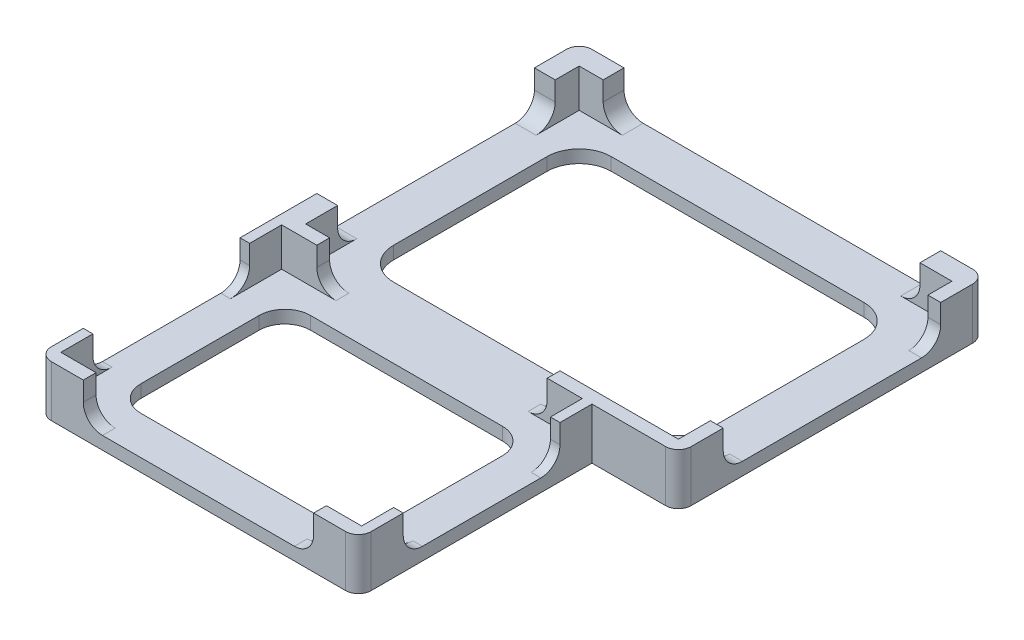
SolidWorks part; units mm, degrees
ref_plane "Front Plane" through (0, 0, 0) normal (0, 0, 1) x (1, 0, 0)
ref_plane "Top Plane" through (0, 0, 0) normal (0, 1, 0) x (1, 0, 0)
ref_plane "Right Plane" through (0, 0, 0) normal (1, 0, 0) x (0, 0, -1)
sketch "Sketch1" plane through (0, 0, 0) normal (0, 1, 0) x (1, 0, 0)
  line L1 (0, 0) -> (63.5, 0)
  line L2 (0, 0) -> (0, 48)
  line L3 (0, 48) -> (63.5, 48)
  line L4 (63.5, 0) -> (63.5, 48)
  dimension "D1" = 63.5
  dimension "D2" = 48
extrude "Boss-Extrude6" add sketch "Sketch1" along normal blind 21
sketch "Sketch5" plane through (0, 0, 0) normal (0, -1, 0) x (-1, 0, 0)
  line L1 (0, 0) -> (-50, 0)
  line L2 (0, 0) -> (0, -38.5)
  line L3 (0, -38.5) -> (-50, -38.5)
  line L4 (-50, 0) -> (-50, -38.5)
  dimension "D1" = 50
  dimension "D2" = 38.5
extrude "Boss-Extrude7" add sketch "Sketch5" against normal blind 11.5
sketch "Sketch6" plane through (0, 21, 0) normal (0, 1, 0) x (1, 0, 0)
  line L0 (63.5, 0) -> (63.5, 48) construction
  line L1 (61.5, 2) -> (2, 2)
  line L2 (61.5, 2) -> (61.5, 46)
  line L3 (61.5, 46) -> (2, 46)
  line L4 (2, 2) -> (2, 46)
  line L5 (63.5, 48) -> (0, 48) construction
  line L6 (0, 0) -> (63.5, 0) construction
  line L7 (0, 48) -> (0, 0) construction
  dimension "D1" = 2
  dimension "D2" = 2
  dimension "D3" = 2
  dimension "D4" = 2
extrude "Cut-Extrude1" cut sketch "Sketch6" against normal blind 19
sketch "Sketch7" plane through (0, 11.5, 0) normal (0, 1, 0) x (1, 0, 0)
  line L0 (50, 0) -> (50, -38.5) construction
  line L1 (48, -34.5) -> (2, -34.5)
  line L2 (48, -34.5) -> (48, 0)
  line L3 (48, 0) -> (2, 0)
  line L4 (2, -34.5) -> (2, 0)
  line L5 (0, -38.5) -> (0, 0) construction
  line L6 (50, -38.5) -> (0, -38.5) construction
  line L7 (0, 0) -> (50, 0) construction
  dimension "D1" = 2
  dimension "D2" = 2
  dimension "D3" = 4
  dimension "D4" = 0
extrude "Cut-Extrude2" cut sketch "Sketch7" against normal blind 9.5
sketch "Sketch8" plane through (0, 0, 38.5) normal (0, 0, 1) x (1, 0, 0)
  line L1 (50, 11.5) -> (0, 11.5)
  line L2 (50, 11.5) -> (50, 0)
  line L3 (50, 0) -> (0, 0)
  line L4 (0, 11.5) -> (0, 0)
extrude "Cut-Extrude4" cut sketch "Sketch8" against normal blind 2 contours L2 L1 L4 L3
sketch "Sketch10" plane through (0, 2, 0) normal (0, 1, 0) x (1, 0, 0)
  line L0 (2, 2) -> (61.5, 2) construction
  line L1 (12, 7) -> (51.5, 7)
  line L2 (7, 12) -> (7, 36)
  line L3 (12, 41) -> (51.5, 41)
  line L4 (56.5, 12) -> (56.5, 36)
  line L5 (2, 46) -> (2, 2) construction
  line L6 (61.5, 2) -> (61.5, 46) construction
  line L7 (61.5, 46) -> (2, 46) construction
  arc A0 (12, 7) -> (7, 12) centre (12, 12) cw
  arc A1 (7, 36) -> (12, 41) centre (12, 36) cw
  arc A2 (51.5, 41) -> (56.5, 36) centre (51.5, 36) cw
  arc A3 (51.5, 7) -> (56.5, 12) centre (51.5, 12) ccw
  dimension "D5" = 5
  dimension "D6" = 5
  dimension "D7" = 5
  dimension "D8" = 5
  dimension "D1" = 5
  dimension "D2" = 5
  dimension "D3" = 5
  dimension "D4" = 5
extrude "Cut-Extrude6" cut sketch "Sketch10" against normal blind 2
sketch "Sketch11" plane through (0, 2, 0) normal (0, 1, 0) x (1, 0, 0)
  line L0 (2, 0) -> (2, -34.5) construction
  line L1 (10, -30.5) -> (40, -30.5)
  line L2 (6, -26.5) -> (6, -8)
  line L3 (10, -4) -> (40, -4)
  line L4 (44, -26.5) -> (44, -8)
  line L5 (2, -34.5) -> (48, -34.5) construction
  line L6 (48, 0) -> (2, 0) construction
  line L7 (48, -34.5) -> (48, 0) construction
  arc A0 (10, -30.5) -> (6, -26.5) centre (10, -26.5) cw
  arc A1 (6, -8) -> (10, -4) centre (10, -8) cw
  arc A2 (40, -4) -> (44, -8) centre (40, -8) cw
  arc A3 (40, -30.5) -> (44, -26.5) centre (40, -26.5) ccw
  dimension "D5" = 4
  dimension "D6" = 4
  dimension "D7" = 4
  dimension "D8" = 4
  dimension "D1" = 4
  dimension "D2" = 4
  dimension "D3" = 4
  dimension "D4" = 4
extrude "Cut-Extrude7" cut sketch "Sketch11" against normal blind 2
sketch "Sketch13" plane through (63.5, 0, 0) normal (1, 0, 0) x (0, 0, -1)
  line L0 (0, 21) -> (48, 21) construction
  line L1 (7, 21) -> (41, 21)
  line L2 (7, 21) -> (7, 5)
  line L3 (10, 2) -> (38, 2)
  line L4 (41, 21) -> (41, 5)
  line L5 (2, 2) -> (2, 21) construction
  line L6 (46, 2) -> (46, 21) construction
  line L7 (2, 2) -> (46, 2) construction
  arc A0 (7, 5) -> (10, 2) centre (10, 5) ccw
  arc A1 (38, 2) -> (41, 5) centre (38, 5) ccw
  dimension "D5" = 3
  dimension "D6" = 3
  dimension "D1" = 0
  dimension "D2" = 5
  dimension "D3" = 5
  dimension "D4" = 0
extrude "Cut-Extrude10" cut sketch "Sketch13" against normal blind 72 contours A1 L3 A0 L2 L1 L4
sketch "Sketch14" plane through (0, 0, -48) normal (0, 0, -1) x (-1, 0, 0)
  line L0 (-61.5, 2) -> (-61.5, 21) construction
  line L1 (-56.5, 21) -> (-7, 21)
  line L2 (-56.5, 21) -> (-56.5, 5)
  line L3 (-53.5, 2) -> (-10, 2)
  line L4 (-7, 21) -> (-7, 5)
  line L5 (-2, 2) -> (-2, 21) construction
  line L6 (-61.5, 2) -> (-2, 2) construction
  line L7 (-63.5, 21) -> (0, 21) construction
  arc A0 (-56.5, 5) -> (-53.5, 2) centre (-53.5, 5) ccw
  arc A1 (-10, 2) -> (-7, 5) centre (-10, 5) ccw
  dimension "D5" = 3
  dimension "D6" = 3
  dimension "D1" = 5
  dimension "D2" = 5
  dimension "D3" = 0
  dimension "D4" = 0
extrude "Cut-Extrude11" cut sketch "Sketch14" against normal blind 38
sketch "Sketch16" plane through (63.5, 0, 0) normal (1, 0, 0) x (0, 0, -1)
  line L0 (41, 21) -> (41, 5) construction
  line L1 (-19, 14.5) -> (48, 14.5)
  line L2 (-19, 14.5) -> (-19, 21)
  line L3 (-19, 21) -> (48, 21)
  line L4 (48, 14.5) -> (48, 21)
  line L5 (48, 21) -> (48, 0) construction
  line L6 (41, 21) -> (48, 21) construction
  line L7 (38, 2) -> (46, 2) construction
  dimension "D1" = 60
  dimension "D2" = 0
  dimension "D3" = 0
  dimension "D4" = 12.5
extrude "Cut-Extrude13" cut sketch "Sketch16" against normal blind 79
sketch "Sketch17" plane through (0, 0, -2) normal (0, 0, -1) x (-1, 0, 0)
  line L0 (-2, 14.5) -> (-61.5, 14.5) construction
  line L1 (-43, 14.5) -> (-7, 14.5)
  line L2 (-43, 14.5) -> (-43, 5)
  line L3 (-40, 2) -> (-10, 2)
  line L4 (-7, 14.5) -> (-7, 5)
  line L5 (-2, 2) -> (-2, 14.5) construction
  line L6 (-48, 2) -> (-48, 11.5) construction
  line L7 (-48, 2) -> (-2, 2) construction
  arc A0 (-10, 2) -> (-7, 5) centre (-10, 5) ccw
  arc A1 (-43, 5) -> (-40, 2) centre (-40, 5) ccw
  dimension "D5" = 3
  dimension "D6" = 3
  dimension "D1" = 0
  dimension "D2" = 5
  dimension "D3" = 5
  dimension "D4" = 0
extrude "Cut-Extrude14" cut sketch "Sketch17" against normal blind 79
sketch "Sketch18" plane through (50, 0, 0) normal (1, 0, 0) x (0, 0, -1)
  line L0 (0, 11.5) -> (-36.5, 11.5) construction
  line L1 (-29.5, 11.5) -> (-5, 11.5)
  line L2 (-29.5, 11.5) -> (-29.5, 5)
  line L3 (-26.5, 2) -> (-8, 2)
  line L4 (-5, 11.5) -> (-5, 5)
  line L5 (0, 0) -> (-36.5, 0) construction
  line L6 (-34.5, 2) -> (-34.5, 11.5) construction
  line L7 (0, 2) -> (0, 11.5) construction
  arc A0 (-29.5, 5) -> (-26.5, 2) centre (-26.5, 5) ccw
  arc A1 (-8, 2) -> (-5, 5) centre (-8, 5) ccw
  dimension "D5" = 3
  dimension "D6" = 3
  dimension "D1" = 0
  dimension "D2" = 2
  dimension "D3" = 5
  dimension "D4" = 5
extrude "Cut-Extrude15" cut sketch "Sketch18" against normal blind 79
fillet "Fillet1" radius 2 1 edges at (50, 5.75, 36.5) type face fillet first side face at (50, 5.8757, 17.65) second side face at (25, 5.8757, 36.5)
fillet "Fillet2" radius 2 1 edges at (0, 5.75, 36.5) type face fillet first side face at (24.6, 5.8757, 36.5) second side face at (0, 7.1953, -3.5278)
fillet "Fillet3" radius 2 1 edges at (0, 7.25, -48) type face fillet first side face at (0, 7.1953, -3.75) second side face at (31.75, 7.0757, -48)
fillet "Fillet4" radius 2 1 edges at (63.5, 7.25, -48) type face fillet first side face at (32.15, 7.0757, -48) second side face at (63.5, 7.0757, -24)
fillet "Fillet5" radius 2 1 edges at (63.5, 7.25, 0) type face fillet first side face at (63.5, 7.0757, -23.6) second side face at (49.9579, 6.7087, 0)
sketch "Sketch19" plane through (50, 0, 0) normal (1, 0, 0) x (0, 0, -1)
  line L0 (-29.5, 11.5) -> (-34.5, 11.5) construction
  line L1 (-36.5, 9.5) -> (0, 9.5)
  line L2 (-36.5, 9.5) -> (-36.5, 11.5)
  line L3 (-36.5, 11.5) -> (0, 11.5)
  line L4 (0, 9.5) -> (0, 11.5)
  line L5 (-26.5, 2) -> (-8, 2) construction
  line L6 (-36.5, 5) -> (-36.5, 11.5) construction
  line L7 (0, 11.5) -> (0, 0) construction
  dimension "D1" = 0
  dimension "D2" = 7.5
  dimension "D3" = 0
  dimension "D4" = 0
extrude "Cut-Extrude17" cut sketch "Sketch19" against normal blind 79
fillet "Fillet6" radius 5 1 edges at (1, 9.5, 0) type face fillet first side face at (1, 9.5, 2.5) second side face at (3.9112, 8.0541, 0)
fillet "Fillet7" radius 5 1 edges at (49, 9.5, 0) type face fillet first side face at (49, 9.5, 2.5) second side face at (49.5135, 6.2643, 0)
sketch "Sketch20" plane through (0, 2, 0) normal (0, 1, 0) x (1, 0, 0)
  line L0 (10, 0) -> (2, 0) construction
  line L1 (23, 0) -> (27, 0)
  line L2 (23, 0) -> (23, 2)
  line L3 (23, 2) -> (27, 2)
  line L4 (27, 0) -> (27, 2)
  line L5 (10, 0) -> (10, 2) construction
  line L6 (40, 0) -> (40, 2) construction
  dimension "D1" = 2
  dimension "D2" = 0
  dimension "D3" = 13
  dimension "D4" = 13
extrude "Boss-Extrude16" add sketch "Sketch20" along normal blind 18
sketch "Sketch30" plane through (0, 0, 0) normal (0, 0, 1) x (1, 0, 0)
  line L0 (23, 20) -> (23, 2) construction
  line L1 (27, 20) -> (23, 20)
  line L2 (27, 20) -> (27, 19)
  line L3 (27, 19) -> (23, 19)
  line L4 (23, 20) -> (23, 19)
  dimension "D1" = 1
extrude "Boss-Extrude17" add sketch "Sketch30" along normal blind 2
sketch "Sketch33" plane through (0, 0, 0) normal (0, 0, 1) x (1, 0, 0)
  line L0 (23, 19) -> (23, 2) construction
  line L1 (23, 12) -> (27, 12)
  line L2 (23, 12) -> (23, 13.5)
  line L3 (23, 13.5) -> (27, 13.5)
  line L4 (27, 12) -> (27, 13.5)
  line L5 (27, 19) -> (27, 2) construction
  line L6 (23, 2) -> (27, 2) construction
  dimension "D1" = 10
  dimension "D2" = 1.5
extrude "Boss-Extrude18" add sketch "Sketch33" along normal blind 4
sketch "Sketch34" plane through (0, 0, -2) normal (0, 0, -1) x (-1, 0, 0)
  line L0 (-23, 20) -> (-23, 2) construction
  line L1 (-27, 20) -> (-23, 20)
  line L2 (-27, 20) -> (-27, 19)
  line L3 (-27, 19) -> (-23, 19)
  line L4 (-23, 20) -> (-23, 19)
  dimension "D1" = 1
extrude "Boss-Extrude19" add sketch "Sketch34" along normal blind 2
sketch "Sketch36" plane through (0, 0, 2) normal (0, 0, 1) x (1, 0, 0)
  line L1 (27, 19) -> (23, 19)
  line L2 (27, 19) -> (27, 20)
  line L3 (27, 20) -> (23, 20)
  line L4 (23, 19) -> (23, 20)
extrude "Cut-Extrude21" cut sketch "Sketch36" against normal blind 2
sketch "Sketch37" plane through (27, 0, 0) normal (1, 0, 0) x (0, 0, -1)
  line L0 (0, 20) -> (4, 19.2571)
  line L1 (0, 20) -> (4, 20) construction
  line L2 (4, 20) -> (4, 19) construction
  line L3 (4, 19.2571) -> (4, 20)
  line L4 (4, 20) -> (0, 20)
extrude "Cut-Extrude22" cut sketch "Sketch37" against normal blind 7
sketch "Sketch38" plane through (27, 0, 0) normal (1, 0, 0) x (0, 0, -1)
  line L0 (0, 13.5) -> (-4, 10.2256)
  line L1 (-4, 12) -> (-4, 13.5) construction
  line L2 (-4, 10.2256) -> (-4, 13.5)
  line L3 (-4, 13.5) -> (0, 13.5)
extrude "Cut-Extrude25" cut sketch "Sketch38" against normal blind 7
sketch "Sketch39" plane through (27, 0, 0) normal (1, 0, 0) x (0, 0, -1)
  line L0 (0, 2) -> (2, 2) construction
  line L1 (-1.8324, 20) -> (7.3799, 20)
  line L2 (-1.8324, 20) -> (-1.8324, 2)
  line L3 (-1.8324, 2) -> (7.3799, 2)
  line L4 (7.3799, 20) -> (7.3799, 2)
  dimension "D1" = 0
  dimension "D2" = 0
  dimension "D3" = 0
extrude "Cut-Extrude26" cut sketch "Sketch39" against normal blind 10
sketch "Sketch40" plane through (0, 0, -48) normal (0, 0, -1) x (-1, 0, 0)
  line L0 (-56.5, 14.5) -> (-61.5, 14.5) construction
  line L1 (-63.5, 14.5) -> (0, 14.5)
  line L2 (-63.5, 14.5) -> (-63.5, 8)
  line L3 (-63.5, 8) -> (0, 8)
  line L4 (0, 14.5) -> (0, 8)
  line L5 (-63.5, 14.5) -> (-63.5, 0) construction
  line L6 (0, 14.5) -> (0, 0) construction
  line L7 (-53.5, 2) -> (-10, 2) construction
  point P9 (0, 11.25)
  dimension "D1" = 0
  dimension "D2" = 0
  dimension "D3" = 0
  dimension "D4" = 6
extrude "Cut-Extrude27" cut sketch "Sketch40" against normal blind 117
sketch "Sketch44" plane through (2, 0, 0) normal (1, 0, 0) x (0, 0, -1)
  line L1 (-34.5, 8) -> (0, 8)
  line L2 (-34.5, 8) -> (-34.5, 2)
  line L3 (-34.5, 2) -> (0, 2)
  line L4 (0, 8) -> (0, 2)
extrude "Cut-Extrude30" cut sketch "Sketch44" against normal blind 0.5
sketch "Sketch45" plane through (48, 0, 0) normal (-1, 0, 0) x (0, 0, 1)
  line L0 (8, 2) -> (0, 2) construction
  line L1 (34.5, 8) -> (0, 8)
  line L2 (34.5, 8) -> (34.5, 2)
  line L3 (34.5, 2) -> (0, 2)
  line L4 (0, 8) -> (0, 2)
extrude "Cut-Extrude31" cut sketch "Sketch45" against normal blind 0.5
sketch "Sketch46" plane through (2, 0, 0) normal (1, 0, 0) x (0, 0, -1)
  line L1 (2, 2) -> (46, 2)
  line L2 (2, 2) -> (2, 8)
  line L3 (2, 8) -> (46, 8)
  line L4 (46, 2) -> (46, 8)
extrude "Boss-Extrude20" add sketch "Sketch46" along normal blind 1.25
sketch "Sketch47" plane through (0, 0, -46) normal (0, 0, 1) x (1, 0, 0)
  line L1 (61.5, 2) -> (3.25, 2)
  line L2 (61.5, 2) -> (61.5, 8)
  line L3 (61.5, 8) -> (3.25, 8)
  line L4 (3.25, 2) -> (3.25, 8)
extrude "Boss-Extrude21" add sketch "Sketch47" along normal blind 1.25
sketch "Sketch48" plane through (2, 0, 0) normal (-1, 0, 0) x (0, 0, 1)
  line L0 (-7, 5) -> (-7, 8) construction
  line L1 (-7, 8) -> (-41, 8)
  line L2 (-7, 8) -> (-7, 5)
  line L3 (-10, 2) -> (-38, 2)
  line L4 (-41, 8) -> (-41, 5)
  line L5 (-41, 8) -> (-41, 5) construction
  line L6 (-10, 2) -> (-38, 2) construction
  arc A0 (-7, 5) -> (-10, 2) centre (-10, 5) cw
  arc A1 (-38, 2) -> (-41, 5) centre (-38, 5) cw
  dimension "D3" = 3
  dimension "D1" = 0
  dimension "D2" = 0
extrude "Cut-Extrude32" cut sketch "Sketch48" against normal blind 1.25
sketch "Sketch49" plane through (0, 0, -46) normal (0, 0, -1) x (-1, 0, 0)
  line L0 (-10, 2) -> (-53.5, 2) construction
  line L1 (-7, 8) -> (-56.5, 8)
  line L2 (-7, 8) -> (-7, 5)
  line L3 (-10, 2) -> (-53.5, 2)
  line L4 (-56.5, 8) -> (-56.5, 5)
  line L5 (-56.5, 8) -> (-56.5, 5) construction
  arc A0 (-53.5, 2) -> (-56.5, 5) centre (-53.5, 5) cw
  arc A1 (-7, 5) -> (-10, 2) centre (-10, 5) cw
  dimension "D3" = 3
  dimension "D1" = 0
  dimension "D2" = 0
extrude "Cut-Extrude33" cut sketch "Sketch49" against normal blind 1.25
